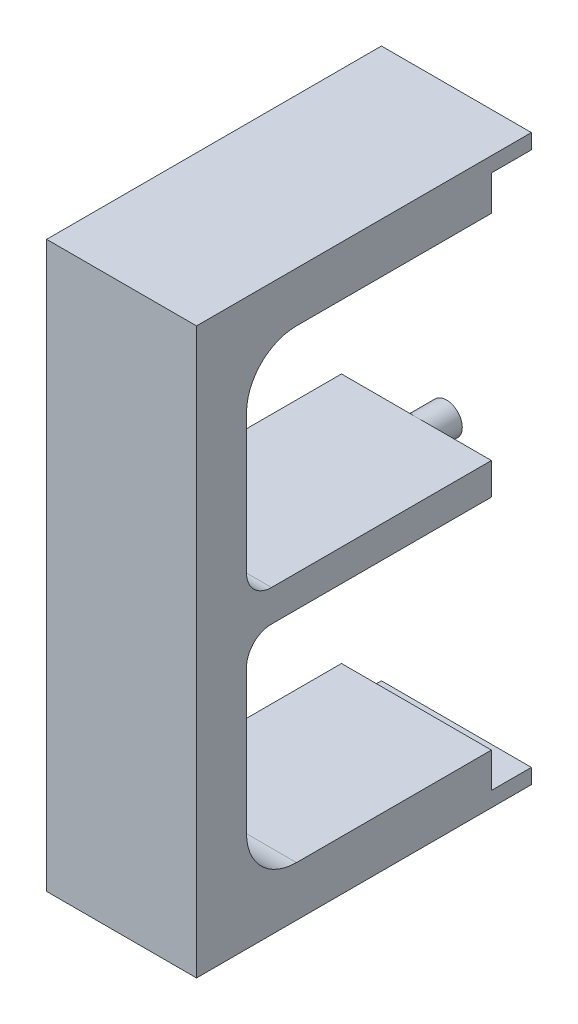
SolidWorks part; units mm, degrees
ref_plane "Front Plane" through (0, 0, 0) normal (0, 0, 1) x (1, 0, 0)
ref_plane "Top Plane" through (0, 0, 0) normal (0, 1, 0) x (1, 0, 0)
ref_plane "Right Plane" through (0, 0, 0) normal (1, 0, 0) x (0, 0, -1)
sketch "Sketch1" plane through (0, 0, 0) normal (0, 0, 1) x (1, 0, 0)
  line L5 (-15, 10) -> (15, 10)
  line L7 (-15, 10) -> (15, 10)
  line L8 (-15, 10) -> (-15, -103)
  line L9 (-15, -103) -> (15, -103)
  line L10 (15, 10) -> (15, -103)
  circle A0 centre (0, -46) radius 3.175
  point P14 (0, 10)
  dimension "D2" = 30
  dimension "D3" = 30
extrude "Boss-Extrude3" add sketch "Sketch1" along normal blind 57 and the other way blind 2 contours L10 L5 L8 L9 A0 | A0 region at (0, 8.8309, 0)
extrude "Boss-Extrude4" add sketch "Sketch1<6>" against normal blind 8 contours A0
sketch "Sketch1<6>" plane through (0, 0, 0) normal (0, 0, 1) x (1, 0, 0) same geometry as "Sketch1"
sketch "Sketch2" plane through (15, 0, 0) normal (1, 0, 0) x (0, 0, -1)
  line L0 (2, 10) -> (-57, 10) construction
  line L1 (2, -42.825) -> (-47, -42.825)
  line L2 (2, -42.825) -> (2, 0)
  line L3 (2, 0) -> (-47, 0)
  line L4 (-47, -42.825) -> (-47, 0)
  line L5 (2, -49.175) -> (-47, -49.175)
  line L6 (2, -49.175) -> (2, -93)
  line L7 (2, -93) -> (-47, -93)
  line L8 (-47, -49.175) -> (-47, -93)
  line L9 (2, -103) -> (-57, -103) construction
  line L10 (-57, 10) -> (-57, -103) construction
  dimension "D1" = 10
  dimension "D2" = 10
  dimension "D3" = 10
  dimension "D4" = 0
extrude "Cut-Extrude1" cut sketch "Sketch2" against normal through all both and the other way through all contours L2 L1 L4 L3 | L6 L5 L8 L7
sketch "Sketch3" plane through (0, 0, -2) normal (0, 0, -1) x (-1, 0, 0)
  line L0 (15, 10) -> (15, 0) construction
  line L1 (-15, 10) -> (15, 10)
  line L2 (-15, 10) -> (-15, 7)
  line L3 (-15, 7) -> (15, 7)
  line L4 (15, 10) -> (15, 7)
  line L5 (15, -93) -> (15, -103) construction
  line L6 (-15, -103) -> (15, -103)
  line L7 (-15, -103) -> (-15, -100)
  line L8 (-15, -100) -> (15, -100)
  line L9 (15, -103) -> (15, -100)
  dimension "D1" = 3
  dimension "D2" = 3
extrude "Boss-Extrude5" add sketch "Sketch3" along normal blind 8
fillet "Fillet2" radius 10 1 edges at (0, 0, 47)
fillet "Fillet3" radius 10 1 edges at (0, -93, 47)
fillet "Fillet4" radius 5 1 edges at (0, -42.825, 47)
fillet "Fillet5" radius 5 1 edges at (0, -49.175, 47)
